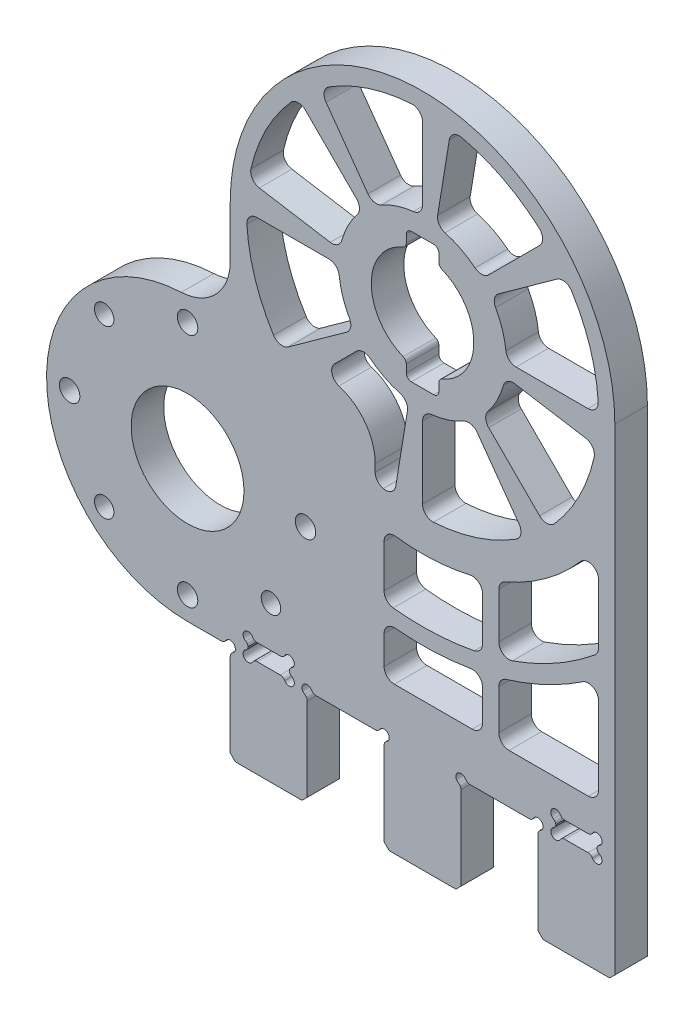
SolidWorks part; units mm, degrees
material "Balsa"
ref_plane "Front Plane" through (0, 0, 0) normal (0, 0, 1) x (1, 0, 0)
ref_plane "Top Plane" through (0, 0, 0) normal (0, 1, 0) x (1, 0, 0)
ref_plane "Right Plane" through (0, 0, 0) normal (1, 0, 0) x (0, 0, -1)
sketch "Sketch1" plane through (0, 0, 0) normal (0, 0, 1) x (1, 0, 0)
  line L0 (-56.9454, 94.4454) -> (-37.5, 75) construction
  line L1 (-40.4988, 0) -> (0, 0)
  line L2 (-75, 55) -> (-75, 75)
  line L3 (-40.4988, 0) -> (-83.323, 0)
  line L4 (0, 0) -> (0, 75)
  line L5 (-37.5, 75) -> (-65, 75) construction
  line L6 (-18.0546, 94.4454) -> (-37.5, 75) construction
  line L7 (-18.0546, 55.5546) -> (-37.5, 75) construction
  line L8 (-75, 55) -> (-83.323, 55)
  line L9 (-83.323, 27.5) -> (-83.323, 50.5) construction
  arc A0 (-75, 75) -> (0, 75) centre (-37.5, 75) cw
  arc A1 (-83.323, 55) -> (-83.323, 0) centre (-83.323, 27.5) ccw
  circle A2 centre (-83.323, 27.5) radius 11
  circle A3 centre (-37.5, 75) radius 10
  circle A4 centre (-83.323, 27.5) radius 23 construction
  circle A5 centre (-67.0596, 11.2365) radius 1.8987
  circle A6 centre (-83.323, 50.5) radius 1.9939
  circle A7 centre (-37.5, 75) radius 27.5 construction
  circle A8 centre (-37.5, 102.5) radius 1.8987 construction
  circle A9 centre (-10, 75) radius 1.8987 construction
  circle A10 centre (-37.5, 47.5) radius 1.8986 construction
  circle A11 centre (-65, 75) radius 1.8987 construction
  circle A12 centre (-56.9454, 94.4454) radius 1.5 construction
  circle A13 centre (-99.5865, 11.2365) radius 1.8987
  circle A14 centre (-60.323, 27.5) radius 1.9939
  circle A15 centre (-99.5865, 43.7635) radius 1.8987
  circle A16 centre (-83.323, 4.5) radius 1.9939
  circle A17 centre (-106.323, 27.5) radius 1.9939
  circle A19 centre (-18.0546, 94.4454) radius 1.5 construction
  circle A20 centre (-18.0546, 55.5546) radius 1.5 construction
  circle A21 centre (-56.9454, 55.5546) radius 1.5 construction
  circle A22 centre (-37.5, 75) radius 14 construction
  circle A23 centre (-37.5, 89) radius 1.5 construction
  circle A24 centre (-51.5, 75) radius 1.5 construction
  circle A25 centre (-37.5, 61) radius 1.5 construction
  circle A26 centre (-23.5, 75) radius 1.5 construction
  circle A28 centre (-67.0596, 43.7635) radius 1.8987 [skipped]
  point P0 (0, 0)
  point P63 (-83.323, 27.5)
  dimension "D3" = 27.5
  dimension "D5" = 20
  dimension "D6" = 22
  dimension "D7" = 46
  dimension "D8" = 3.7973
  dimension "D9" = 3.9878
  dimension "D11" = 55
  dimension "D13" = 3
  dimension "D16" = 3
  dimension "D17" = 4
  dimension "D1" = 75
  dimension "D2" = 66
  dimension "D4" = 75
  dimension "D10" = 4
  dimension "D14" = 45
  dimension "D12" = 4
  dimension "D15" = 4
extrude "Boss-Extrude1" add sketch "Sketch1" along normal blind 6.35
sketch "Sketch2" plane through (0, 0, 0) normal (0, 0, -1) x (-1, 0, 0)
  line L0 (83.323, 0) -> (0, 0) construction
  line L1 (0, 0) -> (15, 0)
  line L2 (0, 0) -> (0, -19.05)
  line L3 (0, -19.05) -> (15, -19.05)
  line L4 (15, 0) -> (15, -19.05)
  line L5 (30, 0) -> (45, 0)
  line L6 (30, 0) -> (30, -19.05)
  line L7 (30, -19.05) -> (45, -19.05)
  line L8 (45, 0) -> (45, -19.05)
  line L10 (60, 0) -> (75, 0)
  line L11 (60, 0) -> (60, -19.05)
  line L12 (60, -19.05) -> (75, -19.05)
  line L13 (75, 0) -> (75, -19.05)
  dimension "D1" = 15
  dimension "D2" = 15
  dimension "D3" = 19.05
  dimension "D4" = 15
extrude "Boss-Extrude2" add sketch "Sketch2" against normal up to surface (6.35 mm away) up to face at (-57.3577, 49.5833, 6.35)
chamfer "Chamfer1" distance 1 angle 45 6 edges at (0, -19.05, 3.175) (-15, -19.05, 3.175) (-30, -19.05, 3.175) (-45, -19.05, 3.175) (-60, -19.05, 3.175) (-75, -19.05, 3.175)
sketch "Sketch3" plane through (0, 0, 6.35) normal (0, 0, 1) x (1, 0, 0)
  line L0 (-83.323, 0) -> (-75, 0) construction
  circle A0 centre (-75, 0) radius 1
  circle A1 centre (-60, 0) radius 1
  circle A2 centre (-45, 0) radius 1
  circle A3 centre (-30, 0) radius 1
  circle A4 centre (-15, 0) radius 1
  dimension "D1" = 2
extrude "Cut-Extrude1" cut sketch "Sketch3" against normal through all
fillet "Fillet1" radius 10 1 edges at (-75, 55, 3.175)
other "Move Face1" [suppressed] offset 0.08 parameters "D1"=0.08
fillet "Fillet2" radius 1 10 edges at (-30, -1, 3.175) (-29, 0, 3.175) (-15, -1, 3.175) (-16, 0, 3.175) (-46, 0, 3.175) (-45, -1, 3.175) (-60, -1, 3.175) (-59, 0, 3.175) (-75, -1, 3.175) (-76, 0, 3.175)
sketch "Sketch4" plane through (0, 0, 6.35) normal (0, 0, 1) x (1, 0, 0)
  line L1 (-71.4967, 0) -> (-63.5033, 0)
  line L2 (-71.4967, 0) -> (-71.4967, 3.2207)
  line L3 (-71.4967, 3.2207) -> (-63.5033, 3.2207)
  line L4 (-63.5033, 0) -> (-63.5033, 3.2207)
  line L7 (-11.4967, 0) -> (-3.5033, 0)
  line L8 (-11.4967, 0) -> (-11.4967, 3.2207)
  line L9 (-11.4967, 3.2207) -> (-3.5033, 3.2207)
  line L10 (-3.5033, 0) -> (-3.5033, 3.2207)
  line L12 (-7.5, -19.05) -> (-7.5, 9.1661) construction
  line L13 (-14, -19.05) -> (-1, -19.05) construction
  line L14 (-67.5, -19.05) -> (-67.5, 15.7141) construction
  line L15 (-74, -19.05) -> (-61, -19.05) construction
  point P14 (-7.5, 0)
  point P19 (-67.5, 0)
  dimension "D1" = 7.9934
  dimension "D2" = 7.9934
  dimension "D3" = 3.2207
  dimension "D6" = 3.2207
extrude "Cut-Extrude2" cut sketch "Sketch4" against normal through all
sketch "Sketch7" plane through (0, 0, 0) normal (0, 0, -1) x (-1, 0, 0)
  line L0 (37.5, 112.5) -> (37.5, -19.05) construction
  line L1 (31, -19.05) -> (44, -19.05) construction
  line L2 (46.7321, 0) -> (46.7321, 54.9725) construction
  line L3 (46.7321, 54.9725) -> (84.5528, 54.9725) construction
  line L4 (50.7784, 65.4603) -> (65.3766, 54.9725)
  line L5 (50.7784, 65.4603) -> (37.5, 75) construction
  line L6 (53.85, 75) -> (71.825, 75)
  line L7 (37.5, 75) -> (53.85, 75) construction
  arc A0 (75, 75) -> (0, 75) centre (37.5, 75) ccw construction
  circle A1 centre (37.5, 75) radius 34.325 construction
  circle A2 centre (37.5, 75) radius 16.35 construction
  arc A3 (65.3766, 54.9725) -> (71.825, 75) centre (37.5, 75) ccw
  circle A4 centre (37.5, 75) radius 10 construction
  arc A5 (50.7784, 65.4603) -> (53.85, 75) centre (37.5, 75) ccw
  dimension "D1" = 3.175
  dimension "D2" = 6.35
extrude "Cut-Extrude5" cut sketch "Sketch7" against normal through all
fillet "Fillet7" radius 2 4 edges at (-50.7784, 65.4603, 3.175) (-65.3766, 54.9725, 3.175) (-71.825, 75, 3.175) (-53.85, 75, 3.175)
pattern_circular "CirPattern1" count 8 over 360 about axis through (-37.5, 75, 6.35) along (0, 0, -1) of "Fillet7", "Cut-Extrude5"
sketch "Sketch10" plane through (0, 0, 0) normal (0, 0, -1) x (-1, 0, 0)
  line L0 (84.5528, 54.9725) -> (46.7321, 54.9725) construction
  line L1 (46.7321, 54.9725) -> (46.7321, 0) construction
  line L2 (56.7321, 54.9725) -> (71.5463, 54.9725)
  line L3 (71.5463, 54.9725) -> (71.5463, 34.3687)
  line L4 (71.5463, 34.3687) -> (46.7321, 34.3687)
  line L5 (46.7321, 34.3687) -> (46.7321, 44.9725)
  arc A0 (46.7321, 44.9725) -> (56.7321, 54.9725) centre (56.7321, 44.9725) cw
  point P11 (71.5463, 34.3687)
  dimension "D1" = 10
extrude "Boss-Extrude3" add sketch "Sketch10" against normal through all
fillet "Fillet12" radius 2 2 edges at (-57.5275, 54.9725, 3.175) (-46.7321, 41.9398, 3.175)
sketch "Sketch11" plane through (0, 0, 6.35) normal (0, 0, 1) x (1, 0, 0)
  circle A0 centre (-71.4967, 3.2207) radius 1
  circle A1 centre (-63.5033, 3.2207) radius 1
  circle A2 centre (-63.5033, 0) radius 1
  circle A3 centre (-71.4967, 0) radius 1
  circle A4 centre (-11.4967, 3.2207) radius 1
  circle A5 centre (-3.5033, 3.2207) radius 1
  circle A6 centre (-3.5033, 0) radius 1
  circle A7 centre (-11.4967, 0) radius 1
  dimension "D1" = 2
extrude "Cut-Extrude6" cut sketch "Sketch11" against normal through all
fillet "Fillet13" radius 1 16 edges at (-71.4967, 2.2207, 3.175) (-71.4967, 1, 3.175) (-70.4967, 0, 3.175) (-64.5033, 0, 3.175) (-63.5033, 1, 3.175) (-63.5033, 2.2207, 3.175) (-64.5033, 3.2207, 3.175) (-70.4967, 3.2207, 3.175) (-4.5033, 3.2207, 3.175) (-3.5033, 2.2207, 3.175) (-3.5033, 1, 3.175) (-4.5033, 0, 3.175) (-10.4967, 0, 3.175) (-11.4967, 1, 3.175) (-11.4967, 2.2207, 3.175) (-10.4967, 3.2207, 3.175)
sketch "Sketch12" plane through (0, 0, 0) normal (0, 0, -1) x (-1, 0, 0)
  line L4 (37.5, 75) -> (56.0106, 75) construction
  line L5 (34.325, 84.4826) -> (34.325, 87.7)
  line L6 (34.325, 87.7) -> (40.675, 87.7)
  line L7 (40.675, 84.4826) -> (40.675, 87.7)
  line L8 (34.325, 84.4826) -> (40.675, 84.4826)
  line L9 (37.5, 75) -> (37.5, 84.4826) construction
  line L10 (34.325, 65.5174) -> (40.675, 65.5174)
  line L11 (40.675, 65.5174) -> (40.675, 62.3)
  line L12 (34.325, 62.3) -> (40.675, 62.3)
  line L13 (34.325, 65.5174) -> (34.325, 62.3)
  circle A0 centre (37.5, 75) radius 10 construction
  dimension "D1" = 6.35
  dimension "D2" = 25.4
extrude "Cut-Extrude7" cut sketch "Sketch12" against normal through all
fillet "Fillet14" radius 1 8 edges at (-34.325, 65.5174, 3.175) (-34.325, 62.3, 3.175) (-40.675, 62.3, 3.175) (-40.675, 65.5174, 3.175) (-40.675, 84.4826, 3.175) (-40.675, 87.7, 3.175) (-34.325, 87.7, 3.175) (-34.325, 84.4826, 3.175)
sketch "Sketch13" plane through (0, 0, 0) normal (0, 0, -1) x (-1, 0, 0)
  line L0 (3.175, 9.5707) -> (45, 9.5707) construction
  line L1 (45, 9.5707) -> (45, 35.0224) construction
  line L2 (3.175, 9.5707) -> (3.175, 53.1768) construction
  line L3 (45, -18.05) -> (45, -1.7321) construction
  line L4 (0, -18.05) -> (0, 75) construction
  line L5 (5.2354, 3.2207) -> (9.7646, 3.2207) construction
  line L6 (22.631, 24.1652) -> (22.631, 37.1401)
  line L7 (3.175, 53.1768) -> (3.175, 34.6632)
  line L8 (25.806, 23.3424) -> (25.806, 36.0422)
  line L9 (45, 35.0224) -> (45, 22.569)
  line L10 (22.631, 20.8652) -> (22.631, 9.5707)
  line L11 (22.631, 9.5707) -> (3.175, 9.5707)
  line L12 (3.175, 9.5707) -> (3.175, 30.5763)
  line L13 (25.806, 20.0917) -> (25.806, 9.5707)
  line L14 (45, 19.3635) -> (45, 9.5707)
  line L15 (45, 9.5707) -> (25.806, 9.5707)
  line L16 (45, 35.0224) -> (3.175, 9.5707) construction
  line L17 (22.631, 24.1652) -> (25.806, 20.0917) construction
  arc A0 (41.2955, 65.7483) -> (41.2955, 84.2517) centre (37.5, 75) ccw construction
  arc A1 (41.2955, 65.7483) -> (41.2955, 84.2517) centre (37.5, 75) ccw construction
  arc A2 (3.175, 53.1768) -> (45, 35.0224) centre (37.5, 75) ccw construction
  arc A3 (8.4377, 93.2644) -> (3.2408, 77.1237) centre (37.5, 75) ccw construction
  arc A4 (22.631, 24.1652) -> (3.175, 34.6632) centre (37.5, 75) cw
  arc A5 (22.631, 37.1401) -> (3.175, 53.1768) centre (37.5, 75) cw
  arc A6 (25.806, 23.3424) -> (45, 22.569) centre (37.5, 75) ccw
  arc A7 (25.806, 36.0422) -> (45, 35.0224) centre (37.5, 75) ccw
  arc A8 (22.631, 20.8652) -> (3.175, 30.5763) centre (37.5, 75) cw
  arc A9 (25.806, 20.0917) -> (45, 19.3635) centre (37.5, 75) ccw
  point P29 (24.0875, 22.2966)
  dimension "D4" = 6.35
  dimension "D6" = 3.175
  dimension "D1" = 0
  dimension "D2" = 3.175
  dimension "D3" = 6.35
  dimension "D5" = 3.175
extrude "Cut-Extrude8" cut sketch "Sketch13" against normal through all
fillet "Fillet15" radius 2 16 edges at (-3.175, 30.5763, 3.175) (-3.175, 9.5707, 3.175) (-22.631, 9.5707, 3.175) (-22.631, 20.8652, 3.175) (-25.806, 20.0917, 3.175) (-25.806, 9.5707, 3.175) (-45, 9.5707, 3.175) (-45, 19.3635, 3.175) (-45, 22.569, 3.175) (-45, 35.0224, 3.175) (-25.806, 36.0422, 3.175) (-25.806, 23.3424, 3.175) (-3.175, 34.6632, 3.175) (-22.631, 24.1652, 3.175) (-22.631, 37.1401, 3.175) (-3.175, 53.1768, 3.175)
